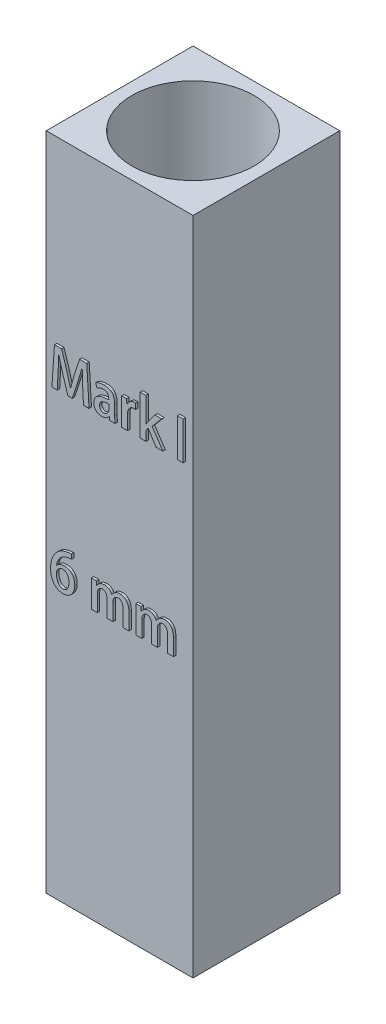
SolidWorks part; units mm, degrees
ref_plane "Alzado" through (0, 0, 0) normal (0, 0, 1) x (1, 0, 0)
ref_plane "Planta" through (0, 0, 0) normal (0, 1, 0) x (1, 0, 0)
ref_plane "Vista lateral" through (0, 0, 0) normal (1, 0, 0) x (0, 0, -1)
sketch "Croquis1" plane through (0, 0, 0) normal (0, 1, 0) x (1, 0, 0)
  line L1 (-3, 3) -> (3, 3)
  line L2 (-3, 3) -> (-3, -3)
  line L3 (-3, -3) -> (3, -3)
  line L4 (3, 3) -> (3, -3)
  line L5 (-3, 3) -> (3, -3) construction
  line L6 (-3, -3) -> (3, 3) construction
  circle A0 centre (0, 0) radius 2.5
  point P0 (0, 0)
  dimension "D1" = 5
  dimension "D2" = 6
extrude "Saliente-Extruir1" add sketch "Croquis1" along normal blind 27
sketch "Croquis2" plane through (0, 0, 3) normal (0, 0, 1) x (1, 0, 0)
  text T0 "Mark I\r\n \r\n6 mm" font "@Adobe Heiti Std R" height in points 5
split line "Línea de partición1"
extrude "Saliente-Extruir2" add sketch "Croquis2<2>" along normal blind 0.1
sketch "Croquis2<2>" plane through (0, 0, 3) normal (0, 0, 1) x (1, 0, 0) same geometry as "Croquis2"
